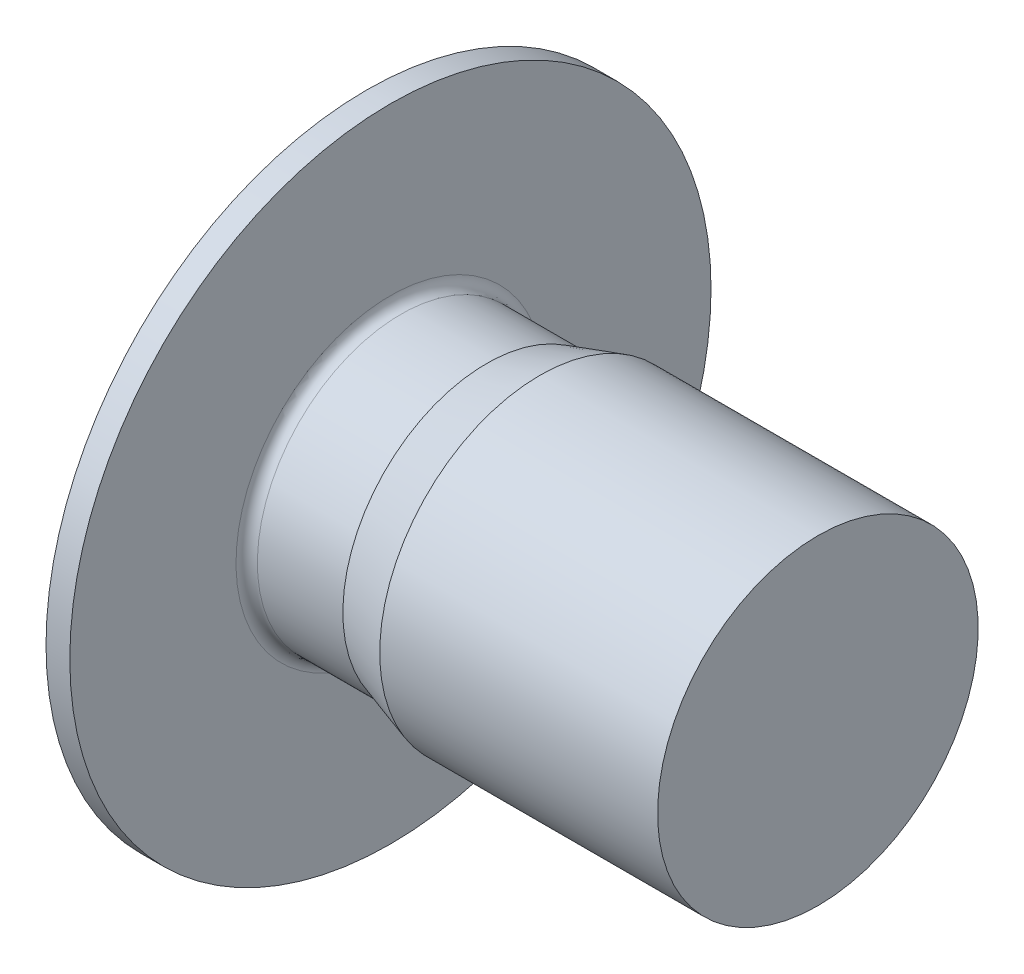
SolidWorks part; units mm, degrees
material "SCM435"
ref_plane "Front Plane" through (0, 0, 0) normal (0, 0, 1) x (1, 0, 0)
ref_plane "Top Plane" through (0, 0, 0) normal (0, 1, 0) x (1, 0, 0)
ref_plane "Right Plane" through (0, 0, 0) normal (1, 0, 0) x (0, 0, -1)
sketch "Sketch1" plane through (0, 0, 0) normal (0, 0, 1) x (1, 0, 0)
  line L0 (-0.8, 0) -> (4, 0) construction
  line L1 (-0.8, 0) -> (-0.8, 2)
  line L2 (-0.2226, 3) -> (0, 3)
  line L3 (0, 3) -> (0, 1.345)
  line L4 (1.4, 1.5) -> (4, 1.5)
  line L5 (4, 1.5) -> (4, 0)
  line L6 (4, 0) -> (-0.8, 0)
  line L7 (1.4, 1.5) -> (0.9, 1.345)
  line L8 (0.9, 1.345) -> (0, 1.345)
  line L9 (-0.2226, 3) -> (-0.8, 2)
  line L10 (-0.8, 0) -> (4, 0) construction
  dimension "A" = 6
  dimension "M" = 3
  dimension "L" = 4
  dimension "E" = 0.8
  dimension "FIX_1" = 30
  dimension "MSM_1" = 4
  dimension "MSM_2" = 2.69
  dimension "MSM_3" = 0.5
  dimension "E_s" = 1.4
revolve "Revolve1" add sketch "Sketch1" angle 360 about L0
cosmetic thread "Thread1" parameters "ATL_1"=2.6, "ATD"=2.459
fillet "Fillet1" radius 0.1 1 edges at (0, -1.345, 0)
sketch "Sketch2" plane through (-0.8, 0, 0) normal (-1, 0, 0) x (0, 0, 1)
  line L1 (0, 0.866) -> (-0.75, 0.433)
  line L2 (-0.75, 0.433) -> (-0.75, -0.433)
  line L3 (-0.75, -0.433) -> (0, -0.866)
  line L4 (0, -0.866) -> (0.75, -0.433)
  line L5 (0.75, -0.433) -> (0.75, 0.433)
  line L6 (0.75, 0.433) -> (0, 0.866)
  circle A0 centre (0, 0) radius 0.75 construction
  dimension "B" = 1.5
extrude "Cut-Extrude1" cut sketch "Sketch2" against normal blind 2
sketch "Sketch3" plane through (0, 0, 0) normal (0, 0, 1) x (1, 0, 0)
  line L0 (1.2, 0) -> (1.6506, 0) construction
  line L1 (1.2, 0) -> (1.2, 0.75)
  line L2 (1.2, 0.75) -> (1.6506, 0)
  line L3 (1.6506, 0) -> (1.2, 0)
  line L5 (1.2, 0.433) -> (1.2, -0.433) construction
  dimension "FIX_3" = 59
  dimension "B" = 1.5
revolve "Cut-Revolve1" cut sketch "Sketch3" angle 360 about L0
equation "\"ATL_1@Thread1\" = \"L@Sketch1\" - \"E_s@Sketch1\""
